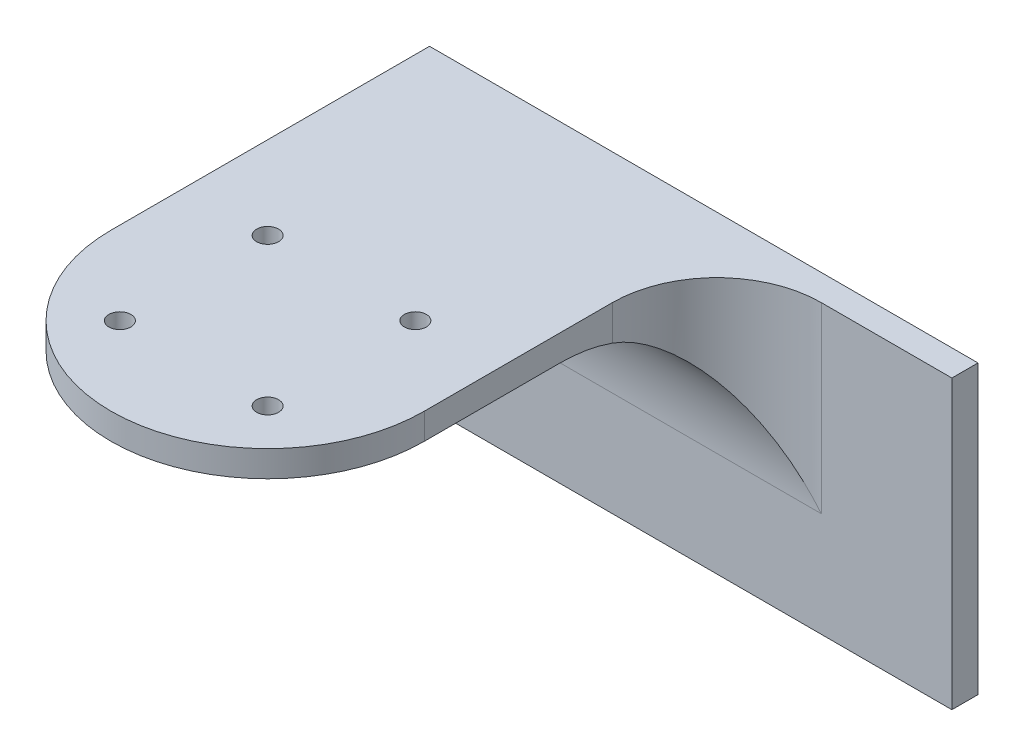
SolidWorks part; units mm, degrees
ref_plane "Front Plane" through (0, 0, 0) normal (0, 0, 1) x (1, 0, 0)
ref_plane "Top Plane" through (0, 0, 0) normal (0, 1, 0) x (1, 0, 0)
ref_plane "Right Plane" through (0, 0, 0) normal (1, 0, 0) x (0, 0, -1)
sketch "Sketch1" plane through (0, 0, 0) normal (0, 1, 0) x (1, 0, 0)
  line L0 (0, 0) -> (-21.2132, 21.2132) construction
  line L1 (0, 0) -> (0, 30) construction
  circle A0 centre (0, 0) radius 30
  circle A1 centre (14.1421, 14.1421) radius 2.1
  circle A2 centre (-14.1421, 14.1421) radius 2.1
  circle A3 centre (-14.1421, -14.1421) radius 2.1
  circle A4 centre (14.1421, -14.1421) radius 2.1
  dimension "D1" = 60
  dimension "D2" = 4.2
  dimension "D4" = 20
  dimension "D3" = 45
  dimension "D5" = 20
extrude "Boss-Extrude1" add sketch "Sketch1" along normal blind 5
sketch "Sketch2" plane through (0, 0, 0) normal (0, -1, 0) x (1, 0, 0)
  line L1 (-30, -61) -> (30, -61)
  line L3 (-30, 0) -> (-30, -61)
  line L4 (30, 0) -> (30, -61)
  circle A0 centre (0, 0) radius 30 construction
  arc A2 (-30, 0) -> (30, 0) centre (0, 0) ccw
  dimension "D1" = 61
extrude "Boss-Extrude2" add sketch "Sketch2" against normal blind 5
sketch "Sketch3" plane through (0, 0, 0) normal (0, -1, 0) x (1, 0, 0)
  line L0 (30, -61) -> (30, 0) construction
  line L1 (-30, -61) -> (30, -61)
  line L2 (-30, -61) -> (-30, -56)
  line L3 (-30, -56) -> (30, -56)
  line L4 (30, -61) -> (30, -56)
  dimension "D1" = 5
extrude "Boss-Extrude3" add sketch "Sketch3" along normal blind 50
fillet "Fillet1" radius 30 1 edges at (0, 0, -56)
sketch "Sketch4" plane through (30, 0, 0) normal (1, 0, 0) x (0, 0, -1)
  line L1 (56, -50) -> (61, -50)
  line L2 (56, -50) -> (56, 5)
  line L3 (56, 5) -> (61, 5)
  line L4 (61, -50) -> (61, 5)
extrude "Boss-Extrude4" add sketch "Sketch4" along normal blind 45
fillet "Fillet2" radius 20 1 edges at (30, -12.5, -56)
